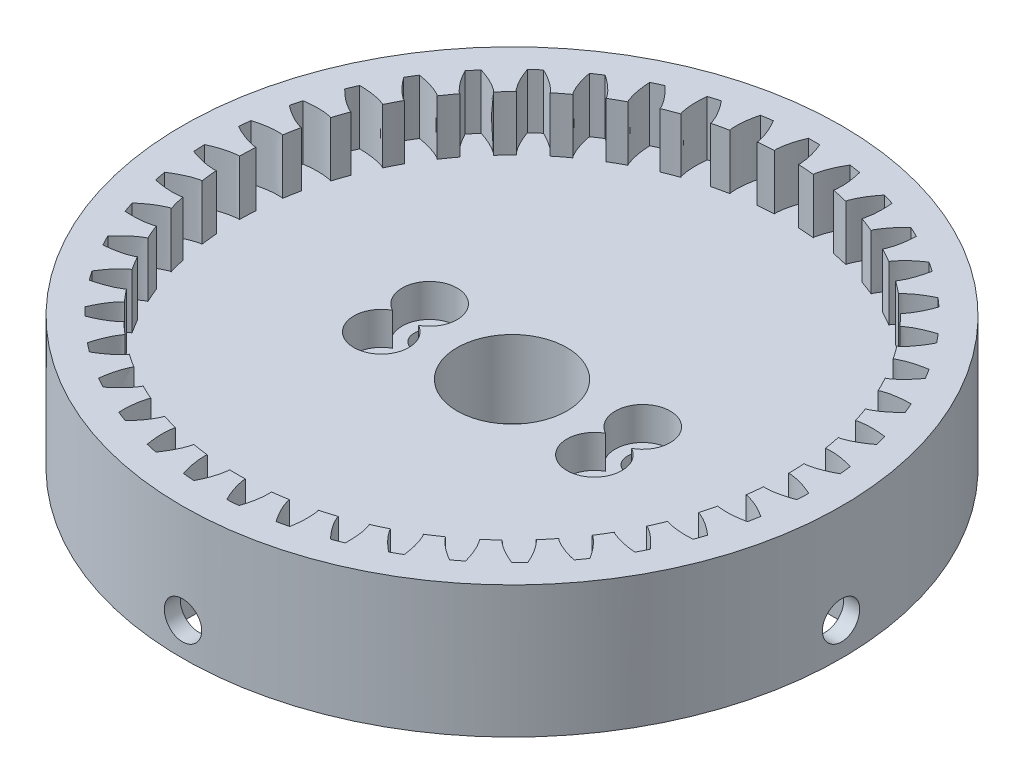
SolidWorks part; units mm, degrees
note: The reader was unsure of these and kept them because the rebuilt part matched: shared geometry of "Sketch1<3>".
ref_plane "Front Plane" through (0, 0, 0) normal (0, 0, 1) x (1, 0, 0)
ref_plane "Top Plane" through (0, 0, 0) normal (0, 1, 0) x (1, 0, 0)
ref_plane "Right Plane" through (0, 0, 0) normal (1, 0, 0) x (0, 0, -1)
sketch "Sketch1" plane through (0, 0, 0) normal (0, 1, 0) x (1, 0, 0)
  line L0 (-12.319, 1.27) -> (-12.319, -1.27) construction
  line L1 (0, 31.75) -> (0, -31.75) construction
  line L2 (12.319, 1.27) -> (12.319, -1.27) construction
  circle A0 centre (0, 0) radius 38.1
  circle A1 centre (0, 0) radius 31.75
  circle A2 centre (-12.319, 2.794) radius 1.524 construction
  circle A3 centre (-12.319, -2.794) radius 1.524 construction
  circle A4 centre (-12.319, 2.794) radius 1.778
  circle A5 centre (-12.319, -2.794) radius 1.778
  circle A6 centre (12.319, -2.794) radius 1.524 construction
  circle A7 centre (12.319, 2.794) radius 1.524 construction
  circle A8 centre (12.319, -2.794) radius 1.778
  circle A9 centre (12.319, 2.794) radius 1.778
  point P11 (-12.319, 0)
  dimension "D1" = 76.2
  dimension "D3" = 10.795
  dimension "D4" = 3.048
  dimension "D5" = 2.54
  dimension "D6" = 3.556
  dimension "D2" = 6.35
extrude "Boss-Extrude1" add sketch "Sketch1" along normal blind 5.08 contours A0 A1 | A1 A8 A5 A4 A9
extrude "Boss-Extrude2" add sketch "Sketch1<3>" along normal blind 11.43 contours A0 A1
sketch "Sketch1<3>" plane through (0, 0, 0) normal (0, 1, 0) x (1, 0, 0) same geometry as "Sketch1"
sketch "Sketch2" plane through (0, 11.43, 0) normal (0, 1, 0) x (1, 0, 0)
  line L0 (0, 31.75) -> (0, 0) construction
  line L1 (0, 0) -> (9.5474, 30.2805) construction
  line L2 (0, 0) -> (6.872, 30.9974) construction
  line L3 (0, 0) -> (4.1442, 31.4784) construction
  line L4 (0, 0) -> (1.3849, 31.7198) construction
  line L5 (0, 0) -> (-1.3849, 31.7198) construction
  line L6 (4.1442, 31.4784) -> (-1.396, 32.2078) construction
  line L7 (6.872, 30.9974) -> (-1.3114, 32.8116) construction
  line L8 (9.5474, 30.2805) -> (-1.1113, 33.6412) construction
  line L9 (1.3849, 31.7198) -> (-1.4064, 31.8417) construction
  line L10 (0, 0) -> (12.1502, 29.3332) construction
  line L11 (0, 0) -> (14.6605, 28.1626) construction
  line L12 (12.1502, 29.3332) -> (-0.7564, 34.6793) construction
  line L13 (14.6605, 28.1626) -> (-0.2093, 35.9033) construction
  line L14 (-38.1, 0) -> (-34.925, 0) construction
  line L15 (-34.925, 0) -> (-31.75, 0) construction
  circle A0 centre (0, 0) radius 31.75 construction
  circle A1 centre (0, 0) radius 31.75 construction
  circle A2 centre (0, 0) radius 31.75 construction
  circle A3 centre (0, 0) radius 22.225
  circle A4 centre (0, 0) radius 34.925
  circle A5 centre (0, 0) radius 38.1 construction
  spline S0 degree 3 poles (-1.3849, 31.7198) (-1.4259, 31.8794) (-1.3968, 32.2496) (-1.3099, 32.8932) (-0.9928, 34.1585) (-0.573, 35.1762) (-0.2093, 35.9033) knots 0 0 0 0 0.111594 0.250457 0.444806 1 1 1 1
  spline S1 degree 3 poles (1.3849, 31.7198) (1.4259, 31.8794) (1.3968, 32.2496) (1.3099, 32.8932) (0.9928, 34.1585) (0.573, 35.1762) (0.2093, 35.9033) knots 0 0 0 0 0.111594 0.250457 0.444806 1 1 1 1
  dimension "D10" = 44.45
  dimension "D2" = 25
  dimension "D1" = 5
  dimension "D3" = 10
  dimension "D4" = 15
  dimension "D5" = 20
  dimension "D6" = 5.588
  dimension "D7" = 8.382
  dimension "D8" = 11.176
  dimension "D9" = 2.794
  dimension "D12" = 30
  dimension "D13" = 13.97
  dimension "D14" = 16.764
extrude "Cut-Extrude1" cut sketch "Sketch2" against normal up to surface (6.35 mm away)
pattern_circular "CirPattern1" count 43 over 360 about axis through (0, 11.43, 0) along (0, -1, 0) of "Cut-Extrude1"
sketch "Sketch4" plane through (0, 0, 0) normal (0, -1, 0) x (1, 0, 0)
  circle A0 centre (12.319, -2.794) radius 1.778 construction
  circle A1 centre (0, 0) radius 38.1
  circle A2 centre (0, 0) radius 38.1
  circle A3 centre (12.319, 2.794) radius 1.778 construction
  circle A4 centre (-12.319, 2.794) radius 1.778 construction
  circle A5 centre (-12.319, -2.794) radius 1.778 construction
  circle A6 centre (12.319, -2.794) radius 1.778
  circle A7 centre (12.319, 2.794) radius 1.778
  circle A8 centre (-12.319, 2.794) radius 1.778
  circle A9 centre (-12.319, -2.794) radius 1.778
  dimension "D1" = 0
extrude "Boss-Extrude3" add sketch "Sketch4" along normal blind 3.81
sketch "Sketch3" plane through (0, 5.08, 0) normal (0, 1, 0) x (1, 0, 0)
  circle A0 centre (-12.319, 2.794) radius 3.175
  circle A1 centre (-12.319, -2.794) radius 3.175
  circle A2 centre (12.319, -2.794) radius 3.175
  circle A3 centre (12.319, 2.794) radius 3.175
  dimension "D1" = 6.35
extrude "Cut-Extrude2" cut sketch "Sketch3" against normal blind 3.81 contours A1 A0 | A0 A1 | A0 A1 | A3 A2 | A2 A3 | A2 A3
sketch "Sketch5" plane through (0, 5.08, 0) normal (0, 1, 0) x (1, 0, 0)
  circle A0 centre (0, 0) radius 6.35
  dimension "D1" = 12.7
extrude "Cut-Extrude3" cut sketch "Sketch5" against normal through all
sketch "Sketch10" plane through (0, -3.81, 0) normal (0, -1, 0) x (1, 0, 0)
  line L0 (36.195, -3.683) -> (32.385, -3.683)
  line L1 (-3.683, 36.195) -> (3.683, 36.195)
  line L2 (-3.683, 36.195) -> (-3.683, 32.385)
  line L3 (-3.683, 32.385) -> (3.683, 32.385)
  line L4 (3.683, 36.195) -> (3.683, 32.385)
  line L5 (-3.683, 36.195) -> (3.683, 32.385) construction
  line L6 (-3.683, 32.385) -> (3.683, 36.195) construction
  line L7 (36.195, 3.683) -> (36.195, -3.683)
  line L8 (36.195, 3.683) -> (32.385, -3.683) construction
  line L9 (32.385, 3.683) -> (36.195, -3.683) construction
  line L10 (32.385, 3.683) -> (32.385, -3.683)
  line L11 (36.195, 3.683) -> (32.385, 3.683)
  line L12 (-3.683, -36.195) -> (-3.683, -32.385)
  line L13 (3.683, -36.195) -> (-3.683, -36.195)
  line L14 (3.683, -36.195) -> (-3.683, -32.385) construction
  line L15 (3.683, -32.385) -> (-3.683, -36.195) construction
  line L16 (3.683, -32.385) -> (-3.683, -32.385)
  line L17 (3.683, -36.195) -> (3.683, -32.385)
  line L18 (-36.195, 3.683) -> (-32.385, 3.683)
  line L19 (-36.195, -3.683) -> (-36.195, 3.683)
  line L20 (-36.195, -3.683) -> (-32.385, 3.683) construction
  line L21 (-32.385, -3.683) -> (-36.195, 3.683) construction
  line L22 (-32.385, -3.683) -> (-32.385, 3.683)
  line L23 (-36.195, -3.683) -> (-32.385, -3.683)
  circle A0 centre (0, 0) radius 38.1 construction
  point P0 (0, 34.29)
  point P9 (-32.385, 0)
  point P23 (0, 0)
  dimension "D1" = 3.81
  dimension "D2" = 7.366
  dimension "D4" = 4
  dimension "D3" = 3.81
  dimension "D5" = 32.385
extrude "Cut-Extrude4" cut sketch "Sketch10" against normal blind 7.62
ref_plane "Plane1" through (0, 5.588, 0) normal (0, 1, 0) x (1, 0, 0)
ref_plane "Plane2" through (0, 5.842, 0) normal (0, 1, 0) x (1, 0, 0)
sketch "Sketch14" plane through (0, 0, -36.195) normal (0, 0, 1) x (1, 0, 0)
  line L0 (0, 11.43) -> (0, -3.81) construction
  line L1 (0, -3.81) -> (0, 0) construction
  line L2 (-3.683, -3.81) -> (3.683, -3.81) construction
  line L3 (0, 0) -> (0, 3.81) construction
  line L4 (-3.683, 3.81) -> (3.683, 3.81) construction
  circle A0 centre (0, 0) radius 2.159
  dimension "D1" = 4.318
extrude "Cut-Extrude5" cut sketch "Sketch14" against normal up to next
pattern_circular "CirPattern2" count 4 over 360 about axis through (0, 5.08, 0) along (0, -1, 0) of "Cut-Extrude5"
sketch "Sketch12" plane through (0, -3.81, 0) normal (0, -1, 0) x (1, 0, 0)
  circle A0 centre (0, 0) radius 38.735
  circle A1 centre (0, 0) radius 38.1
  circle A2 centre (0, 0) radius 38.1
  circle A3 centre (0, 0) radius 42.545
  dimension "D1" = 0
  dimension "D2" = 0.635
  dimension "D3" = 3.81
